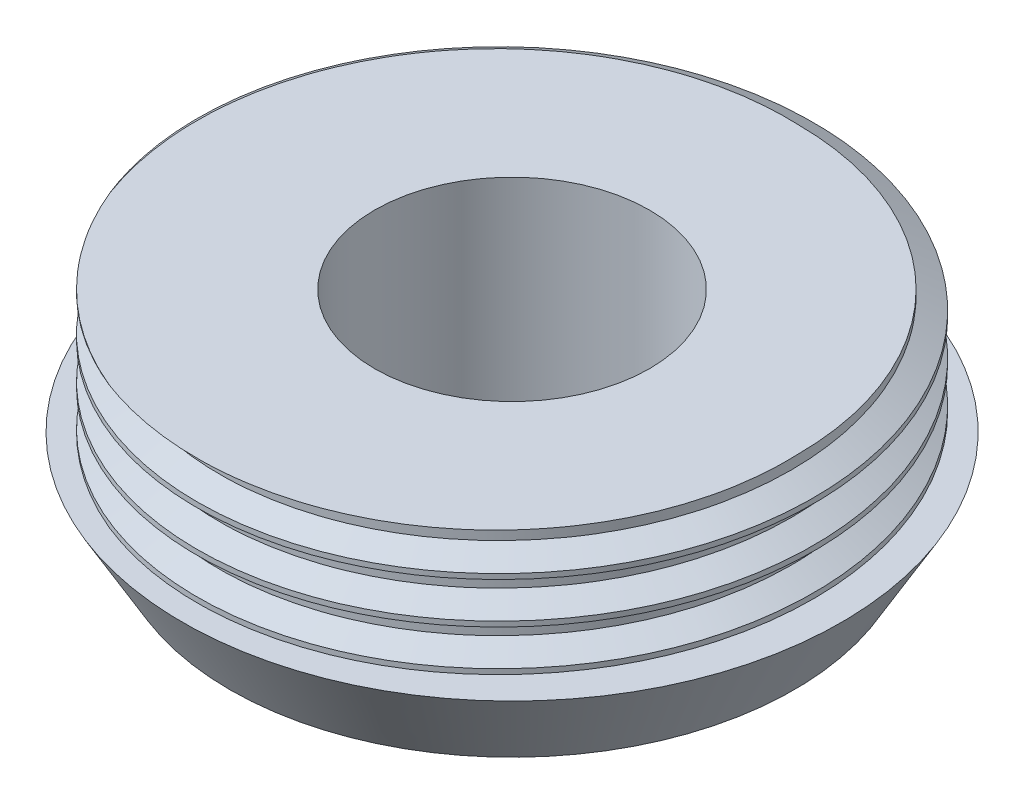
SolidWorks part; units mm, degrees
ref_plane "Front Plane" through (0, 0, 0) normal (0, 0, 1) x (1, 0, 0)
ref_plane "Top Plane" through (0, 0, 0) normal (0, 1, 0) x (1, 0, 0)
ref_plane "Right Plane" through (0, 0, 0) normal (1, 0, 0) x (0, 0, -1)
sketch "Sketch1" plane through (0, 0, 0) normal (0, 0, 1) x (1, 0, 0)
  line L0 (-14.685, 0) -> (-14.685, 6.35)
  line L4 (-14.685, 0) -> (-16.94, 0)
  line L5 (-16.94, 0) -> (-14.5, -4.2262)
  line L6 (-14.5, -4.2262) -> (-7.065, -4.2262)
  line L9 (-14.685, 6.35) -> (-7.065, 6.35)
  line L11 (-7.065, -4.2262) -> (-7.065, 6.35)
  line L12 (0, 0) -> (0, 16.9845) construction
  dimension "D1" = 14.685
  dimension "D2" = 6.35
  dimension "D3" = 16.94
  dimension "D4" = 14.5
  dimension "D5" = 7.62
  dimension "D6" = 60
revolve "Revolve1" add sketch "Sketch1" angle 360 about L12
thread "Thread1" pitch 2.1167 method extrude trim with start face yes trim with end face yes profile "Thread Profile1" start angle 0, offset 2.1167, length 12.7, pitch 2.1167, diameter 29.37
ref_plane "Plane1" through (14.685, -2.1167, 0) normal (0, 0, 1) x (1, 0, 0)
sketch "Thread Profile1" plane through (14.685, -2.1167, 0) normal (0, 0, 1) x (1, 0, 0)
  line L0 (0, 0) -> (0, 2.1167) construction
  line L1 (0, 0) -> (1.1457, 0.6615)
  line L2 (1.1457, 0.6615) -> (1.1457, 0.926)
  line L3 (1.1457, 0.926) -> (0, 1.5875)
  line L4 (1.1457, 0.7937) -> (0, 0.7937) construction
  line L11 (0, 0) -> (0, 1.5875)
  point P2 (0, 0)
  dimension "Pitch" = 2.1167
  dimension "Profile_Angle" = 60
  dimension "Profile_Land" = 0.2646
  dimension "Profile_Height" = 1.1457
